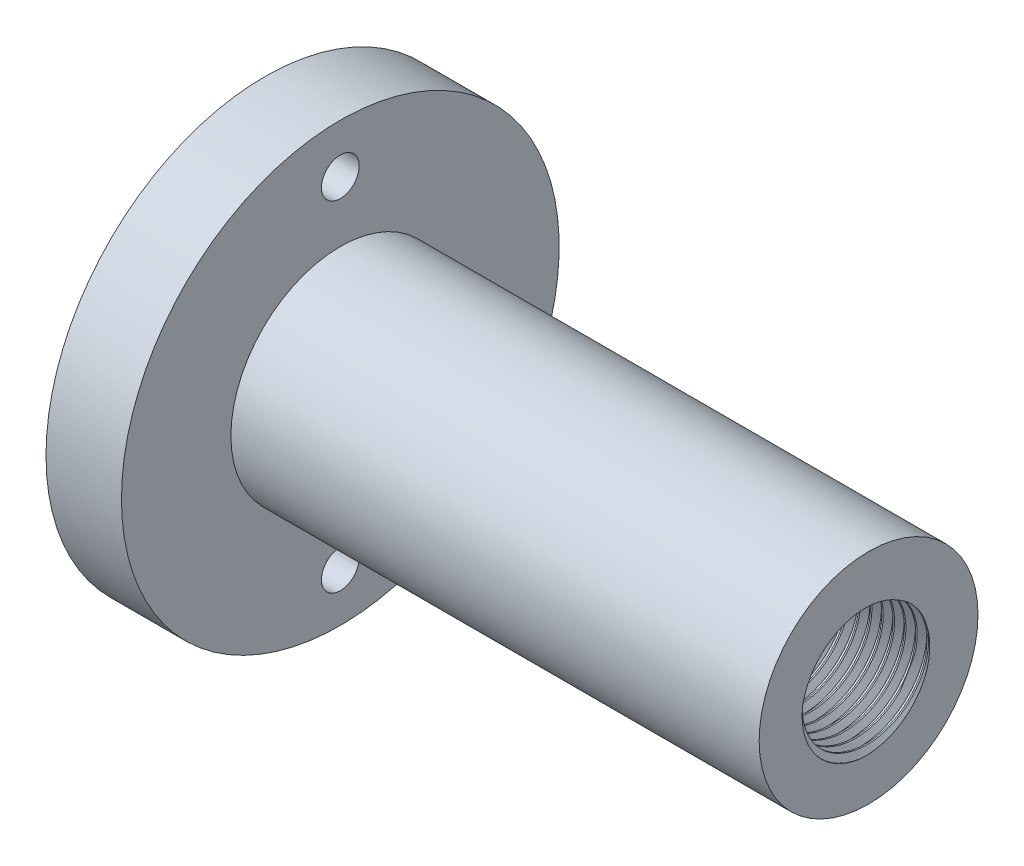
SolidWorks part; units mm, degrees
ref_plane "Front Plane" through (0, 0, 0) normal (0, 0, 1) x (1, 0, 0)
ref_plane "Top Plane" through (0, 0, 0) normal (0, 1, 0) x (1, 0, 0)
ref_plane "Right Plane" through (0, 0, 0) normal (1, 0, 0) x (0, 0, -1)
sketch "Sketch1" plane through (0, 0, 0) normal (0, 0, 1) x (1, 0, 0)
  line L0 (0, 0) -> (12722.8307, 0) construction
  line L1 (0, 0) -> (0, -12722.8307) construction
  line L2 (-48, 29) -> (-38, 29)
  line L3 (-38, 29) -> (-38, 14.5)
  line L4 (-38, 14.5) -> (32, 14.5)
  line L5 (32, 14.5) -> (32, 8)
  line L6 (32, 8) -> (0, 8)
  line L7 (0, 8) -> (0, 13)
  line L8 (0, 13) -> (-44, 13)
  line L10 (-48, 17) -> (-48, 29)
  line L11 (-44, 13) -> (-48, 17)
  point P13 (-48, 13)
  dimension "D1" = 16
  dimension "D2" = 29
  dimension "D3" = 32
  dimension "D4" = 10
  dimension "D5" = 26
  dimension "D6" = 58
  dimension "D7" = 48
  dimension "D8" = 4
  dimension "D9" = 45
revolve "Revolve1" add sketch "Sketch1" angle 360 about L0
sketch "Sketch2" plane through (-48, 0, 0) normal (-1, 0, 0) x (0, 0, 1)
  circle A0 centre (0, 22.5) radius 2.5
  circle A1 centre (0, -22.5) radius 2.5
  circle A2 centre (0, 0) radius 22.5 construction
  dimension "D1" = 45
  dimension "D2" = 5
extrude "Cut-Extrude1" cut sketch "Sketch2" against normal up to next and the other way through all
thread "Thread1" pitch 1.5 profile "Thread Profile1" start angle 0, offset 5, length 155, pitch 1.5, diameter 16
ref_plane "Plane1" through (37, 0, 8) normal (0, 1, 0) x (0, 0, -1)
sketch "Thread Profile1" plane through (37, 0, 8) normal (0, 1, 0) x (0, 0, -1)
  line L0 (0, 0) -> (0, 1.5) construction
  line L11 (0, 0) -> (0, 1.3125)
  line L12 (0, 1.3125) -> (-0.8119, 0.8437)
  line L13 (-0.8119, 0.8437) -> (-0.8119, 0.4687)
  line L15 (-0.8119, 0.4687) -> (0, 0)
  line L17 (-0.8119, 0.6562) -> (0, 0.6562) construction
  point P2 (0, 0)
  dimension "Pitch" = 1.5
  dimension "Profile_Angle" = 60
  dimension "Profile_Land" = 0.375
  dimension "Profile_Height" = 0.8119
